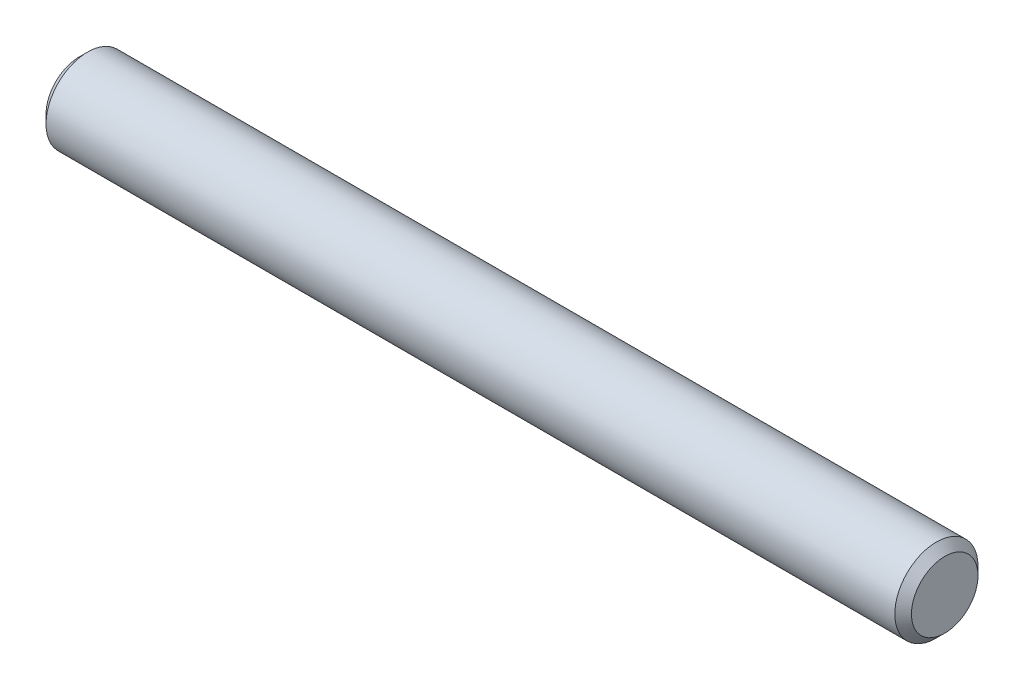
SolidWorks part; units mm, degrees
ref_plane "Front Plane" through (0, 0, 0) normal (0, 0, 1) x (1, 0, 0)
ref_plane "Top Plane" through (0, 0, 0) normal (0, 1, 0) x (1, 0, 0)
ref_plane "Right Plane" through (0, 0, 0) normal (1, 0, 0) x (0, 0, -1)
sketch "Sketch1" plane through (0, 0, 0) normal (0, 1, 0) x (1, 0, 0)
  line L1 (0, 0) -> (-52, 0)
  line L2 (0, 0) -> (0, 2.5)
  line L3 (0, 2.5) -> (-52, 2.5)
  line L4 (-52, 0) -> (-52, 2.5)
  dimension "D1" = 52
  dimension "D2" = 2.5
revolve "Revolve1" add sketch "Sketch1" angle 360 about L1
sketch "Sketch2" plane through (0, 0, 0) normal (0, 1, 0) x (1, 0, 0)
  line L0 (-52, 2) -> (-42, 2)
  line L1 (-52, 2.5) -> (-52, -2.5) construction
  line L2 (-42, 2) -> (-42, 2.5)
  line L3 (0, 2.5) -> (-52, 2.5) construction
  line L4 (-42, 2.5) -> (-52, 2.5)
  line L5 (-52, 2.5) -> (-52, 2)
  line L6 (-52, 0) -> (0, 0) construction
  dimension "D1" = 10
  dimension "D2" = 2
extrude "Cut-Extrude1" cut sketch "Sketch2" against normal through all both and the other way through all
chamfer "Chamfer1" distance 0.5 angle 45 2 edges at (0, 0, -2.5) (-52, 0, 2.5)
